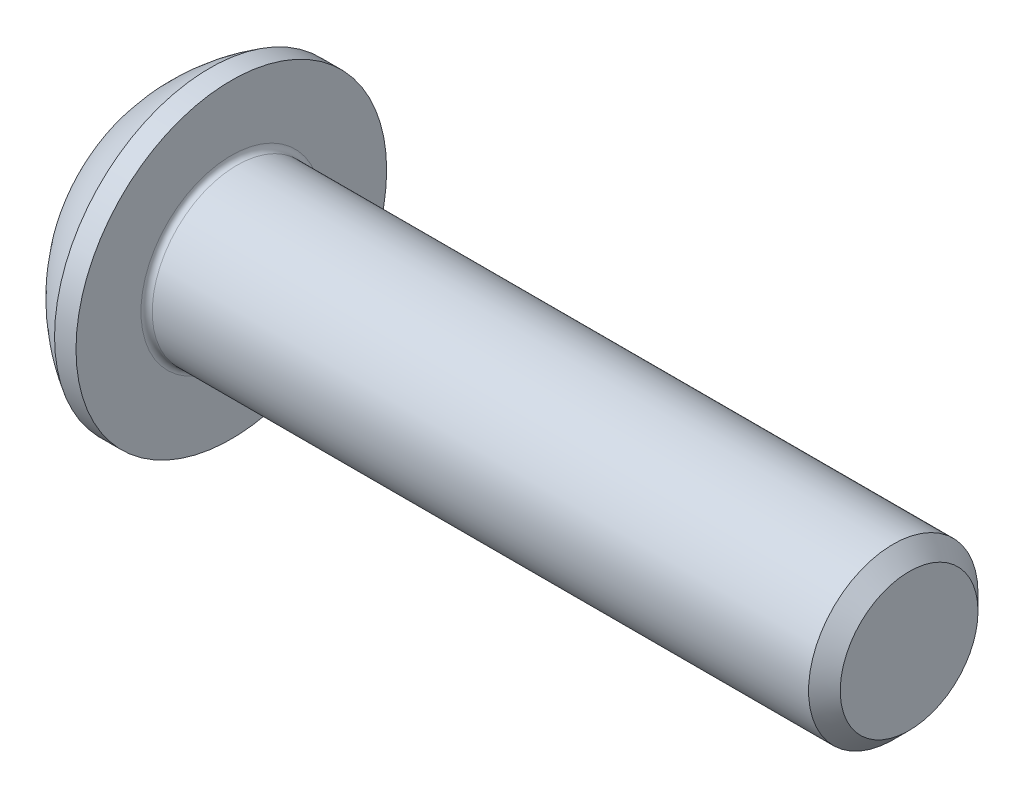
SolidWorks part; units mm, degrees
ref_plane "Front Plane" through (0, 0, 0) normal (0, 0, 1) x (1, 0, 0)
ref_plane "Top Plane" through (0, 0, 0) normal (0, 1, 0) x (1, 0, 0)
ref_plane "Right Plane" through (0, 0, 0) normal (1, 0, 0) x (0, 0, -1)
ref_plane "Plane1" through (0, 0, 0) normal (0, 0, -1) x (-1, 0, 0)
sketch "Sketch1" plane through (0, 0, 0) normal (0, 0, -1) x (-1, 0, 0)
  line L0 (-1.65, 2.75) -> (-1.65, 0)
  line L1 (-1.65, 0) -> (0, 0)
  line L2 (0, 0) -> (0, 1.425)
  line L3 (-1.27, 2.75) -> (-1.65, 2.75)
  line L4 (-1.65, 0) -> (0, 0) construction
  arc A0 (0, 1.425) -> (-1.27, 2.75) centre (-2.962, -0.1429) ccw
  point P6 (0, 0)
  dimension "D5" = 3.3514
  dimension "D1" = 2.75
  dimension "D2" = 1.65
  dimension "D3" = 1.425
  dimension "D4" = 0.38
revolve "Revolve1" add sketch "Sketch1" angle 360 about L4 reverse direction yes
sketch "Sketch2" plane through (0, 0, 0) normal (-1, 0, 0) x (0, 0, 1)
  line L7 (-1, 0.5774) -> (-1, -0.5774)
  line L8 (-1, -0.5774) -> (0, -1.1547)
  line L9 (0, -1.1547) -> (1, -0.5774)
  line L10 (1, -0.5774) -> (1, 0.5774)
  line L11 (1, 0.5774) -> (0, 1.1547)
  line L12 (0, 1.1547) -> (-1, 0.5774)
  circle A0 centre (0, 0) radius 1 construction
  point P7 (0, 0)
  point P10 (0, 0)
  dimension "D1" = 2
extrude "Cut-Extrude1" cut sketch "Sketch2" against normal blind 1.04
sketch "Sketch3" plane through (0, 0, 0) normal (0, 0, 1) x (1, 0, 0)
  line L0 (1.04, 1) -> (1.04, 0)
  line L1 (1.04, 0) -> (1.6174, 0)
  line L2 (1.6174, 0) -> (1.04, 1)
  line L3 (1.04, 0) -> (1.6174, 0) construction
revolve "Cut-Revolve1" cut sketch "Sketch3" angle 360 about L3 reverse direction yes
sketch "Sketch4" plane through (1.65, 0, 0) normal (1, 0, 0) x (0, 0, -1)
  circle A0 centre (0, 0) radius 1.5
extrude "Largo y Ancho rosca" add sketch "Sketch4" along normal blind 12
fillet "Fillet1" radius 0.1 1 edges at (1.65, 0, -1.5) tangent propagation no
chamfer "Chamfer1" distance 0.2805 angle 45 1 edges at (13.65, 0, -1.5)
